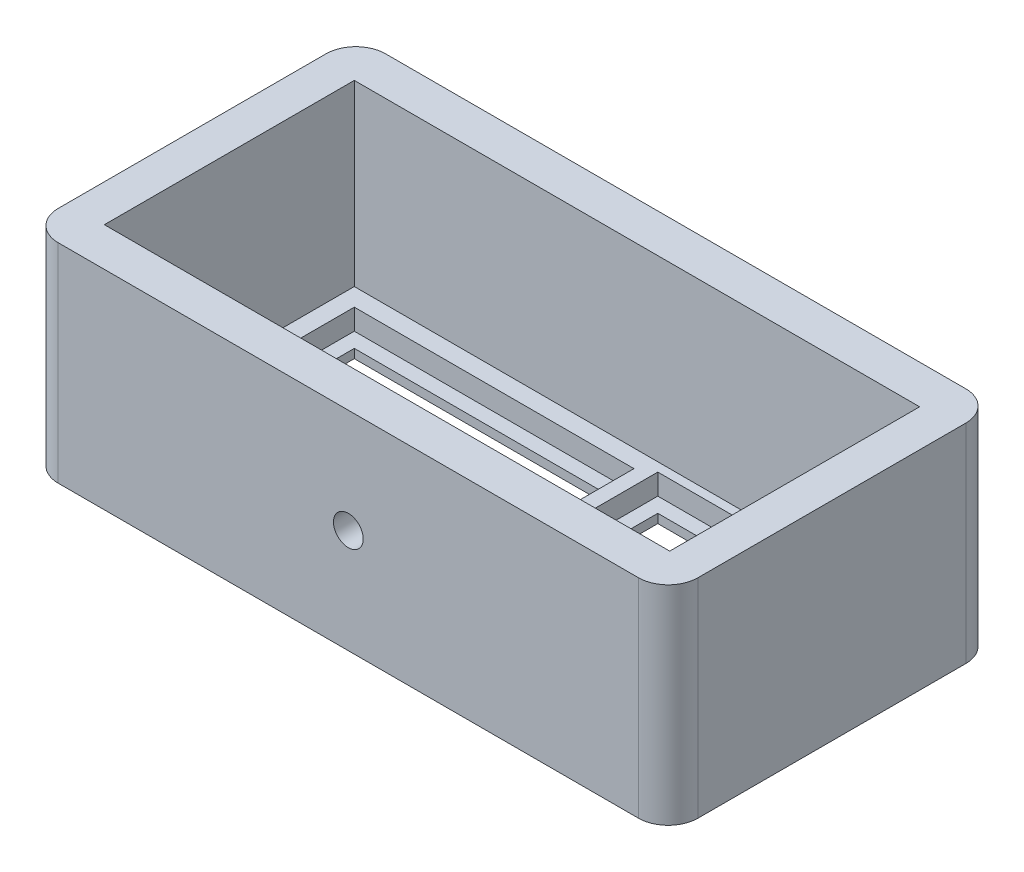
SolidWorks part; units mm, degrees
ref_plane "Front Plane" through (0, 0, 0) normal (0, 0, 1) x (1, 0, 0)
ref_plane "Top Plane" through (0, 0, 0) normal (0, 1, 0) x (1, 0, 0)
ref_plane "Right Plane" through (0, 0, 0) normal (1, 0, 0) x (0, 0, -1)
sketch "Sketch1" plane through (0, 0, 0) normal (0, 1, 0) x (1, 0, 0)
  line L1 (19.5, -11) -> (-19.5, -11)
  line L2 (21.5, -9) -> (21.5, 9)
  line L3 (19.5, 11) -> (-19.5, 11)
  line L4 (-21.5, -9) -> (-21.5, 9)
  line L5 (21.5, -11) -> (-21.5, 11) construction
  line L6 (21.5, 11) -> (-21.5, -11) construction
  arc A0 (19.5, 11) -> (21.5, 9) centre (19.5, 9) cw
  arc A1 (21.5, -9) -> (19.5, -11) centre (19.5, -9) cw
  arc A2 (-19.5, -11) -> (-21.5, -9) centre (-19.5, -9) cw
  arc A3 (-21.5, 9) -> (-19.5, 11) centre (-19.5, 9) cw
  point P0 (0, 0)
  dimension "D3" = 2
  dimension "D1" = 43
  dimension "D2" = 22
extrude "Boss-Extrude1" add sketch "Sketch1" along normal blind 2
sketch "Sketch2" plane through (0, 2, 0) normal (0, 1, 0) x (1, 0, 0)
  line L1 (-17.8, 7.2) -> (1, 7.2)
  line L2 (-17.8, 7.2) -> (-17.8, -8)
  line L3 (-17.8, -8) -> (1, -8)
  line L4 (1, 7.2) -> (1, -8)
  line L5 (2, 7.8) -> (17.8, 7.8)
  line L6 (2, 7.8) -> (2, -8)
  line L7 (2, -8) -> (17.8, -8)
  line L8 (17.8, 7.8) -> (17.8, -8)
  line L10 (-19.5, -11) -> (19.5, -11) construction
  line L14 (-21.5, 9) -> (-21.5, -9) construction
  point P16 (-8.4, -8)
  dimension "D1" = 18.8
  dimension "D2" = 15.2
  dimension "D3" = 15.8
  dimension "D4" = 15.8
  dimension "D5" = 1
  dimension "D6" = 3
  dimension "D7" = 3.7
  dimension "D8" = 3
extrude "Cut-Extrude1" cut sketch "Sketch2" against normal blind 1.4
sketch "Sketch3" plane through (0, 0.6, 0) normal (0, 1, 0) x (1, 0, 0)
  line L0 (1, 7.2) -> (-17.8, 7.2) construction
  line L1 (-16.8, 6.2) -> (0, 6.2)
  line L2 (-16.8, 6.2) -> (-16.8, -7)
  line L3 (-16.8, -7) -> (0, -7)
  line L4 (0, 6.2) -> (0, -7)
  line L5 (3, 6.8) -> (16.8, 6.8)
  line L6 (3, 6.8) -> (3, -7)
  line L7 (3, -7) -> (16.8, -7)
  line L8 (16.8, 6.8) -> (16.8, -7)
  line L9 (-17.8, 7.2) -> (-17.8, -8) construction
  line L10 (-17.8, -8) -> (1, -8) construction
  line L11 (1, -8) -> (1, 7.2) construction
  line L12 (17.8, 7.8) -> (2, 7.8) construction
  line L13 (17.8, -8) -> (17.8, 7.8) construction
  line L14 (2, 7.8) -> (2, -8) construction
  line L15 (2, -8) -> (17.8, -8) construction
  dimension "D1" = 1
  dimension "D2" = 1
  dimension "D3" = 1
  dimension "D4" = 1
  dimension "D5" = 1
  dimension "D6" = 1
  dimension "D7" = 1
  dimension "D8" = 1
extrude "Cut-Extrude2" cut sketch "Sketch3" against normal through all
sketch "Sketch13" plane through (0, 2, 0) normal (0, 1, 0) x (1, 0, 0)
  line L8 (18.5, 8) -> (-18.5, 8)
  line L9 (-18.5, 8) -> (-18.5, -8)
  line L10 (-18.5, -8) -> (18.5, -8)
  line L11 (18.5, -8) -> (18.5, 8)
  line L12 (17.5, 8) -> (-17.5, 8)
  line L13 (-18.5, 7) -> (-18.5, -7)
  line L14 (-17.5, -8) -> (17.5, -8)
  line L15 (18.5, -7) -> (18.5, 7)
  arc A0 (-18.5, 7) -> (-17.5, 8) centre (-17.5, 7) cw
  arc A1 (-17.5, -8) -> (-18.5, -7) centre (-17.5, -7) cw
  arc A2 (17.5, -8) -> (18.5, -7) centre (17.5, -7) ccw
  arc A3 (18.5, 7) -> (17.5, 8) centre (17.5, 7) ccw
  dimension "D2" = 1
  dimension "D1" = 3
extrude "Boss-Extrude3" add sketch "Sketch13" along normal blind 12
fillet "Fillet1" radius 10 1 edges at (17.8, 8, 7.9539)
sketch "Sketch15" plane through (0, 2, 0) normal (0, 1, 0) x (1, 0, 0)
  line L1 (19, -8.4) -> (-19, -8.4)
  line L2 (19, -8.4) -> (19, 8.4)
  line L3 (19, 8.4) -> (-19, 8.4)
  line L4 (-19, -8.4) -> (-19, 8.4)
  line L5 (19, -8.4) -> (-19, 8.4) construction
  line L6 (19, 8.4) -> (-19, -8.4) construction
  point P0 (0, 0)
  dimension "D1" = 16.8
  dimension "D2" = 38
extrude "Cut-Extrude3" cut sketch "Sketch15" along normal through all
sketch "Sketch17" plane through (0, 0, 11) normal (0, 0, 1) x (1, 0, 0)
  line L0 (-19.5, 14) -> (19.5, 14) construction
  line L2 (-21.5, 14) -> (-21.5, 0) construction
  circle A0 centre (0, 7) radius 1
  dimension "D2" = 2
  dimension "D1" = 7
  dimension "D3" = 21.5
extrude "Cut-Extrude5" cut sketch "Sketch17" against normal up to next
